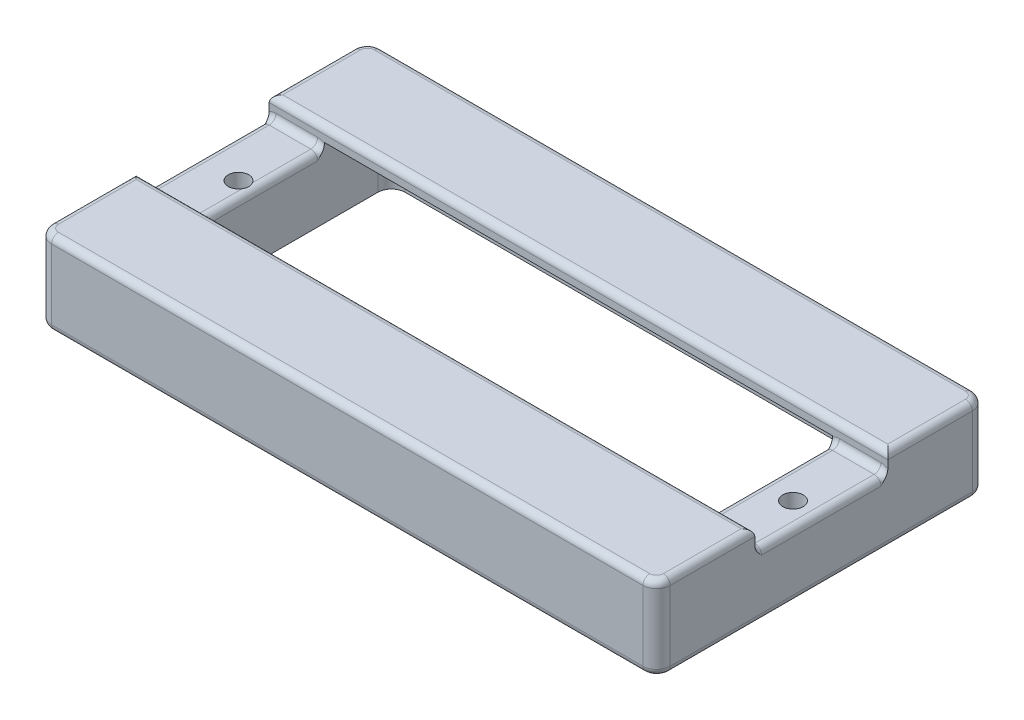
SolidWorks part; units mm, degrees
ref_plane "Front Plane" through (0, 0, 0) normal (0, 0, 1) x (1, 0, 0)
ref_plane "Top Plane" through (0, 0, 0) normal (0, 1, 0) x (1, 0, 0)
ref_plane "Right Plane" through (0, 0, 0) normal (1, 0, 0) x (0, 0, -1)
sketch "Sketch1" plane through (0, 0, 0) normal (0, 1, 0) x (1, 0, 0)
  line L0 (-45.35, 23.655) -> (45.35, 23.655)
  line L1 (-37.25, 19.085) -> (37.25, 19.085)
  line L2 (-37.25, 19.085) -> (-37.25, -19.085)
  line L3 (-37.25, -19.085) -> (37.25, -19.085)
  line L4 (37.25, 19.085) -> (37.25, -19.085)
  line L5 (-37.25, 19.085) -> (37.25, -19.085) construction
  line L6 (-37.25, -19.085) -> (37.25, 19.085) construction
  line L11 (45.35, 23.655) -> (45.35, -24.645)
  line L12 (45.35, -24.645) -> (-45.35, -24.645)
  line L13 (-45.35, 23.655) -> (-45.35, -24.645)
  point P0 (0, 0)
  point P6 (0, 0)
  dimension "D1" = 8.1
  dimension "D2" = 8.1
  dimension "D3" = 4.57
  dimension "D4" = 5.56
  dimension "D5" = 90.7
  dimension "D6" = 48.3
extrude "Boss-Extrude1" add sketch "Sketch1" along normal blind 12.25
sketch "Sketch2" plane through (0, 12.25, 0) normal (0, 1, 0) x (1, 0, 0)
  line L0 (45.35, -24.645) -> (45.35, 23.655) construction
  line L1 (45.35, 9.255) -> (-45.35, 9.255)
  line L2 (45.35, 9.255) -> (45.35, 23.655)
  line L3 (45.35, 23.655) -> (-45.35, 23.655)
  line L4 (-45.35, 9.255) -> (-45.35, 23.655)
  line L6 (-45.35, -24.645) -> (45.35, -24.645)
  line L7 (-45.35, -24.645) -> (-45.35, -10.245)
  line L8 (-45.35, -10.245) -> (45.35, -10.245)
  line L9 (45.35, -24.645) -> (45.35, -10.245)
  dimension "D1" = 14.4
  dimension "D2" = 14.4
extrude "Boss-Extrude2" add sketch "Sketch2" against normal blind 2
sketch "Sketch3" plane through (0, 12.25, 0) normal (0, 1, 0) x (1, 0, 0)
  line L0 (-45.35, 23.655) -> (-45.35, -24.645) construction
  line L1 (-45.35, -10.245) -> (-37.25, -10.245)
  line L2 (-45.35, -10.245) -> (-45.35, 9.255)
  line L3 (-45.35, 9.255) -> (-37.25, 9.255)
  line L4 (-37.25, -10.245) -> (-37.25, 9.255)
  line L5 (45.35, -24.645) -> (45.35, 23.655) construction
  line L6 (45.35, 9.255) -> (37.25, 9.255)
  line L7 (45.35, 9.255) -> (45.35, -10.245)
  line L8 (45.35, -10.245) -> (37.25, -10.245)
  line L9 (37.25, 9.255) -> (37.25, -10.245)
  line L10 (37.25, -10.245) -> (37.25, 9.255) construction
  point P15 (0, 0)
  point P16 (37.25, 6.1569)
extrude "Cut-Extrude1" cut sketch "Sketch3" against normal blind 2.85
sketch "Sketch4" plane through (0, 0, 0) normal (0, -1, 0) x (1, 0, 0)
  line L0 (-45.35, 24.645) -> (45.35, 24.645) construction
  line L1 (-45.35, -23.655) -> (-45.35, 24.645) construction
  line L2 (45.35, 24.645) -> (45.35, -23.655) construction
  line L3 (45.35, -23.655) -> (-45.35, -23.655) construction
  circle A0 centre (-39.55, 21.045) radius 1.5
  circle A1 centre (41.75, 21.045) radius 1.5
  circle A2 centre (41.75, -17.855) radius 1.5
  circle A3 centre (-39.55, -17.855) radius 1.5
  point P8 (0, 0)
  point P9 (0, 0)
  point P14 (-41.5521, 30.4197)
  dimension "D5" = 3
  dimension "D1" = 3.6
  dimension "D2" = 5.8
  dimension "D3" = 3.6
  dimension "D4" = 5.8
extrude "Cut-Extrude2" cut sketch "Sketch4" against normal blind 6.5
sketch "Sketch5" plane through (0, 0, 0) normal (0, -1, 0) x (1, 0, 0)
  circle A0 centre (-39.55, 1.045) radius 1.5
  circle A1 centre (41.75, 1.045) radius 1.5
  circle A2 centre (-39.55, 21.045) radius 1.5 construction
  circle A3 centre (-39.55, 21.045) radius 1.5 construction
  circle A4 centre (41.75, 21.045) radius 1.5 construction
  circle A5 centre (41.75, 21.045) radius 1.5 construction
  point P10 (0, 0)
  dimension "D1" = 3
  dimension "D2" = 20
extrude "Cut-Extrude3" cut sketch "Sketch5" against normal through all
fillet "Fillet7" radius 1 12 edges at (45.35, 12.25, 17.445) (0, 12.25, 10.245) (0, 12.25, 24.645) (-45.35, 12.25, 17.445) (0, 12.25, -9.255) (0, 12.25, -23.655) (45.35, 12.25, -16.455) (-45.35, 12.25, -16.455) (0, 0, 24.645) (0, 0, -23.655) (-45.35, 0, 0.495) (45.35, 0, 0.495)
fillet "Fillet4" radius 2 16 edges at (-45.0571, 11.9571, 24.3521) (-45.0571, 0.2929, 24.3521) (-45.0571, 11.9571, -23.3621) (-45.0571, 0.2929, -23.3621) (45.0571, 11.9571, -23.3621) (45.0571, 0.2929, -23.3621) (45.0571, 11.9571, 24.3521) (45.0571, 0.2929, 24.3521) (-45.35, 6.125, 24.645) (-45.35, 6.125, -23.655) (45.35, 6.125, -23.655) (45.35, 6.125, 24.645) (-37.25, 5.125, 19.085) (37.25, 5.125, 19.085) (-37.25, 5.125, -19.085) (37.25, 5.125, -19.085)
fillet "Fillet5" radius 1 4 edges at (45.35, 9.4, 0.495) (37.25, 9.4, 0.495) (-37.25, 9.4, 0.495) (-45.35, 9.4, 0.495)
fillet "Fillet8" radius 1 12 edges at (45.0571, 9.1071, -9.255) (37.5429, 9.1071, -9.255) (37.5429, 9.1071, 10.245) (45.0571, 9.1071, 10.245) (-45.0571, 9.1071, 10.245) (-37.5429, 9.1071, 10.245) (-37.5429, 9.1071, -9.255) (-45.0571, 9.1071, -9.255) (41.3, 9.4, -9.255) (41.3, 9.4, 10.245) (-41.3, 9.4, 10.245) (-41.3, 9.4, -9.255)
